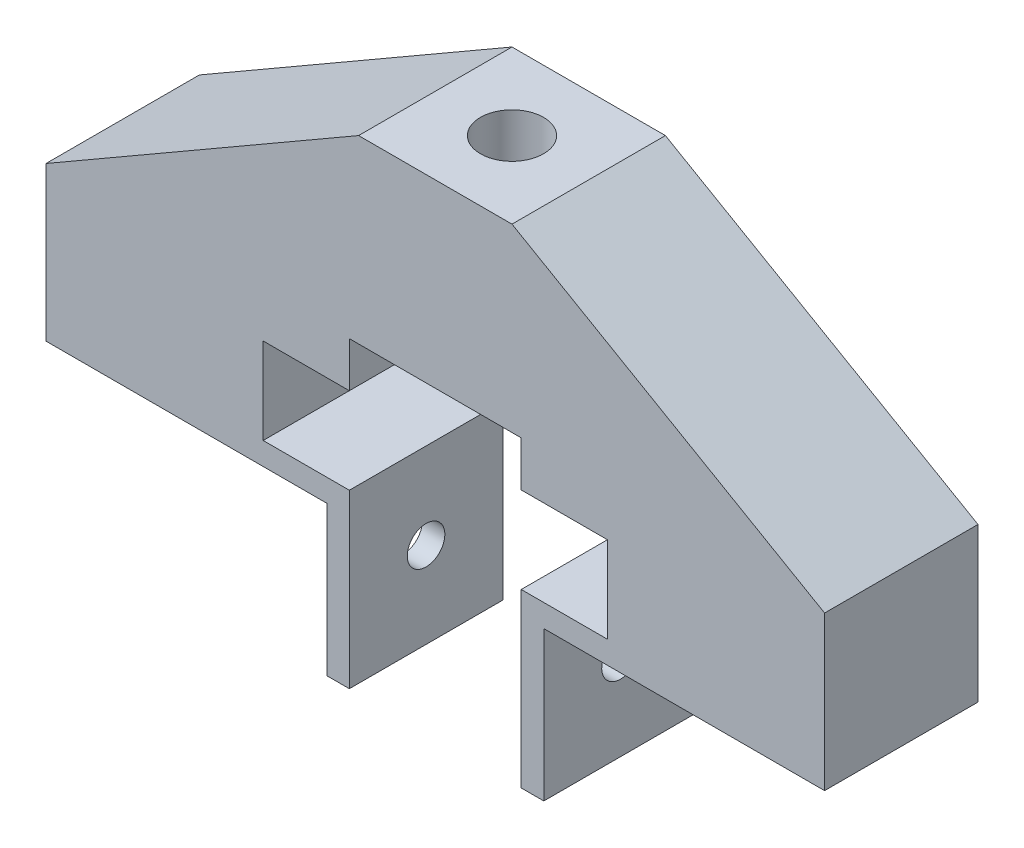
SolidWorks part; units mm, degrees
ref_plane "Front Plane" through (0, 0, 0) normal (0, 0, 1) x (1, 0, 0)
ref_plane "Top Plane" through (0, 0, 0) normal (0, 1, 0) x (1, 0, 0)
ref_plane "Right Plane" through (0, 0, 0) normal (1, 0, 0) x (0, 0, -1)
sketch "Sketch1" plane through (0, 0, 0) normal (0, 0, 1) x (1, 0, 0)
  line L0 (-86.282, 0) -> (-24.05, 0)
  line L1 (-24.05, 0) -> (-24.05, -33.1)
  line L2 (-24.05, -33.1) -> (-19.05, -33.1)
  line L3 (-19.05, -33.1) -> (-19.05, 5)
  line L4 (-19.05, 5) -> (-38.15, 5)
  line L5 (-38.15, 5) -> (-38.15, 24.1)
  line L6 (-38.15, 24.1) -> (-19.05, 24.1)
  line L7 (38.15, 24.1) -> (38.15, 5)
  line L8 (38.15, 5) -> (19.05, 5)
  line L9 (19.05, 5) -> (19.05, -33.1)
  line L10 (19.05, -33.1) -> (24.05, -33.1)
  line L11 (24.05, -33.1) -> (24.05, 0)
  line L12 (24.05, 0) -> (86.282, 0)
  line L13 (86.282, 34.1) -> (17, 74.1)
  line L14 (17, 74.1) -> (-17, 74.1)
  line L15 (-17, 74.1) -> (-86.282, 34.1)
  line L16 (-19.05, 24.1) -> (-19.05, 34.1)
  line L17 (-19.05, 34.1) -> (19.05, 34.1)
  line L18 (19.05, 34.1) -> (19.05, 24.1)
  line L19 (19.05, 24.1) -> (38.15, 24.1)
  line L20 (86.282, 34.1) -> (-86.282, 34.1) construction
  line L21 (-86.282, 34.1) -> (-86.282, 0)
  line L22 (86.282, 34.1) -> (86.282, 0)
  point P18 (0, 74.1)
  point P22 (0, 34.1)
  dimension "D1" = 30
  dimension "D2" = 10
  dimension "D3" = 34
  dimension "D4" = 38.1
  dimension "D5" = 76.3
  dimension "D6" = 19.1
  dimension "D7" = 5
  dimension "D8" = 5
  dimension "D9" = 38.1
  dimension "D10" = 38.1
  dimension "D11" = 40
extrude "Boss-Extrude1" add sketch "Sketch1" along normal blind 34
sketch "Sketch2" plane through (0, 74.1, 0) normal (0, 1, 0) x (1, 0, 0)
  line L0 (-17, 0) -> (17, -34) construction
  line L1 (17, 0) -> (-17, -34) construction
  circle A0 centre (0, -17) radius 7
  dimension "D1" = 14
extrude "Cut-Extrude1" cut sketch "Sketch2" against normal blind 35
sketch "Sketch3" plane through (24.05, 0, 0) normal (1, 0, 0) x (0, 0, -1)
  line L0 (-17, -33.1) -> (-17, 0) construction
  line L1 (-34, -33.1) -> (0, -33.1) construction
  line L2 (-34, 0) -> (0, 0) construction
  circle A0 centre (-17, -14.05) radius 4.1656
  point P12 (0, 0)
  dimension "D1" = 8.3312
  dimension "D2" = 19.05
extrude "Cut-Extrude2" cut sketch "Sketch3" against normal through all
